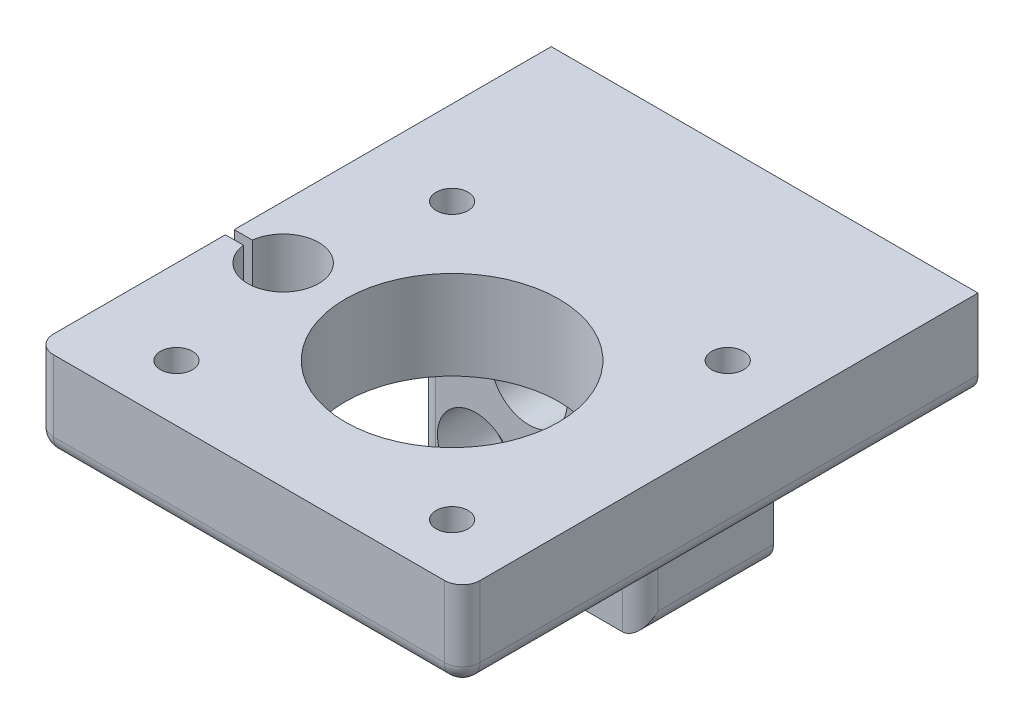
SolidWorks part; units mm, degrees
ref_plane "Front Plane" through (0, 0, 0) normal (0, 0, 1) x (1, 0, 0)
ref_plane "Top Plane" through (0, 0, 0) normal (0, 1, 0) x (1, 0, 0)
ref_plane "Right Plane" through (0, 0, 0) normal (1, 0, 0) x (0, 0, -1)
sketch "Sketch1" plane through (0, 0, 0) normal (0, 1, 0) x (1, 0, 0)
  line L0 (25, -36.15) -> (6, -36.15) construction
  line L1 (0, 0) -> (48, 0)
  line L2 (0, 0) -> (0, -58)
  line L3 (0, -58) -> (48, -58)
  line L4 (48, 0) -> (48, -58)
  line L5 (40.5, -20.65) -> (9.5, -20.65) construction
  line L6 (9.5, -20.65) -> (9.5, -51.65) construction
  line L7 (9.5, -51.65) -> (40.5, -51.65) construction
  line L8 (40.5, -51.65) -> (40.5, -20.65) construction
  line L9 (0, -35.65) -> (2.0314, -35.65)
  line L10 (2.0314, -35.65) -> (2.0314, -36.65)
  line L11 (2.0314, -36.65) -> (0, -36.65)
  line L12 (2.0314, -36.15) -> (6, -36.15) construction
  circle A1 centre (6, -36.15) radius 4
  circle A2 centre (25, -36.15) radius 12
  circle A5 centre (9.5, -20.65) radius 1.8
  circle A6 centre (9.5, -51.65) radius 1.8
  circle A7 centre (40.5, -51.65) radius 1.8
  circle A8 centre (40.5, -20.65) radius 1.8
  dimension "D3" = 8
  dimension "D4" = 24
  dimension "D6" = 19
  dimension "D7" = 23
  dimension "D8" = 3.6
  dimension "D10" = 6.35
  dimension "D1" = 48
  dimension "D2" = 58
  dimension "D5" = 21.85
  dimension "D9" = 31
  dimension "D11" = 7.5
  dimension "D12" = 1
extrude "Boss-Extrude1" add sketch "Sketch1" along normal blind 10 contours L4 L1 L2 L3 region at (24, 0, 0.7529)
sketch "Sketch2" plane through (0, 0, 0) normal (-1, 0, 0) x (0, 0, 1)
  line L1 (0, 0) -> (15, 0)
  line L2 (0, 0) -> (0, -28)
  line L3 (0, -28) -> (15, -28)
  line L4 (15, 0) -> (15, -28)
  dimension "D1" = 28
  dimension "D2" = 15
extrude "Boss-Extrude2" add sketch "Sketch2" against normal blind 25
sketch "Sketch3" plane through (0, 0, 15) normal (0, 0, 1) x (1, 0, 0)
  line L0 (12.5, -8.8038) -> (6.5, -19.1962) construction
  line L1 (6.5, -19.1962) -> (18.5, -19.1962) construction
  line L2 (18.5, -19.1962) -> (12.5, -8.8038) construction
  line L3 (12.5, -19.1962) -> (12.5, -28) construction
  line L4 (25, -28) -> (0, -28) construction
  line L5 (12.5, -8.8038) -> (12.5, 0) construction
  line L6 (25, 0) -> (0, 0) construction
  circle A0 centre (12.5, -8.8038) radius 2.8
  circle A1 centre (6.5, -19.1962) radius 2.8
  circle A2 centre (18.5, -19.1962) radius 2.8
  dimension "D1" = 5.6
  dimension "D2" = 12
extrude "Cut-Extrude1" cut sketch "Sketch3" against normal up to surface (15 mm away) up to face at (24.3333, -6, 0)
sketch "Sketch4" plane through (0, 0, 15) normal (0, 0, 1) x (1, 0, 0)
  circle A0 centre (12.5, -8.8038) radius 4.3
  circle A1 centre (6.5, -19.1962) radius 4.3
  circle A2 centre (18.5, -19.1962) radius 4.3
  dimension "D1" = 8.6
extrude "Cut-Extrude2" cut sketch "Sketch4" against normal blind 6
fillet "Fillet1" radius 2 10 edges at (48, 0, 29) (25, -14, 15) (24, 0, 58) (0, 0, 47.325) (0, 0, 25.325) (0, -14, 15) (0, -28, 7.5) (25, -28, 7.5) (48, 5, 58) (0, 5, 58)
